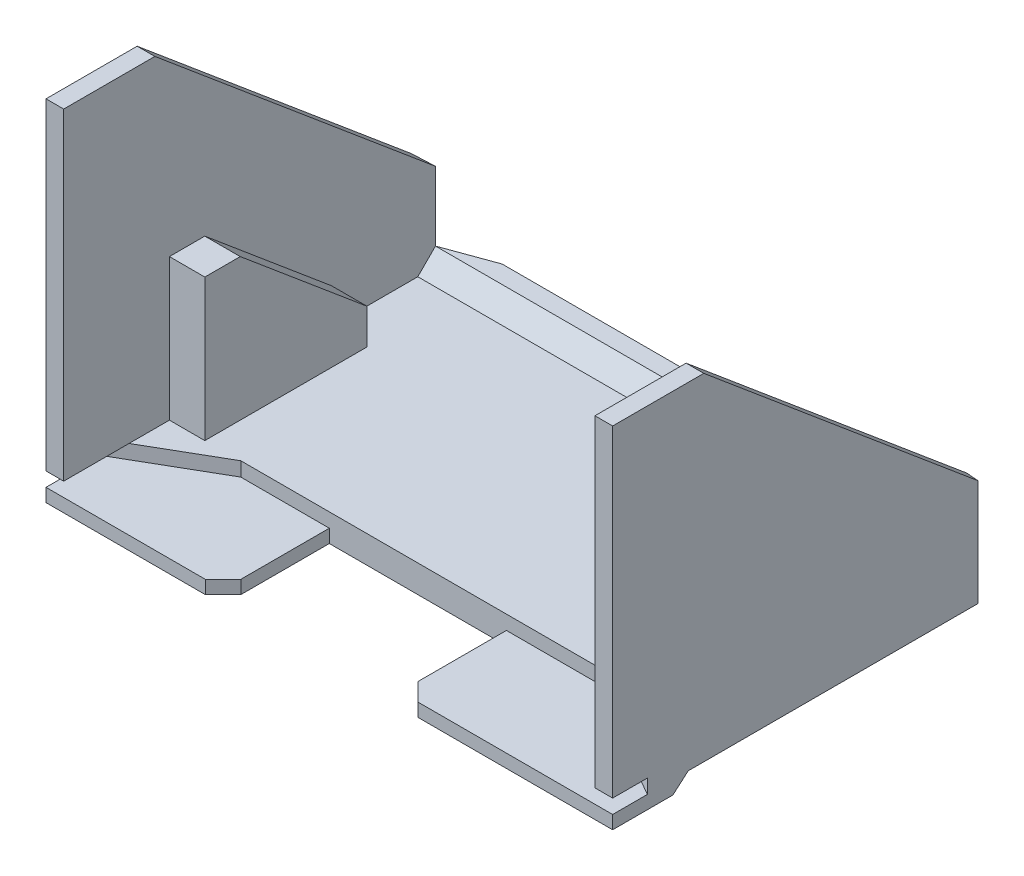
SolidWorks part; units mm, degrees
ref_plane "Front Plane" through (0, 0, 0) normal (0, 0, 1) x (1, 0, 0)
ref_plane "Top Plane" through (0, 0, 0) normal (0, 1, 0) x (1, 0, 0)
ref_plane "Right Plane" through (0, 0, 0) normal (1, 0, 0) x (0, 0, -1)
sketch "Sketch1" plane through (0, 0, 0) normal (1, 0, 0) x (0, 0, -1)
  line L0 (0, 38) -> (0, 0)
  line L1 (0, 0) -> (44, 0)
  line L2 (44, 0) -> (44, 9.7173)
  line L3 (44, 9.7173) -> (10.294, 38)
  line L4 (10.294, 38) -> (0, 38)
  dimension "D1" = 44
  dimension "D2" = 38
  dimension "D3" = 40
  dimension "D4" = 44
extrude "Boss-Extrude1" add sketch "Sketch1" along normal blind 34 and the other way blind 30
sketch "Sketch2" plane through (0, 38, 0) normal (0, 1, 0) x (1, 0, 0)
  line L1 (-30, 44) -> (34, 44) construction
  line L4 (32, 44) -> (-28, 44)
  line L8 (-28, 44) -> (-28, 0)
  line L9 (-30, 0) -> (34, 0) construction
  line L10 (-28, 0) -> (32, 0)
  line L11 (32, 0) -> (32, 44)
  line L12 (-30, 44) -> (-30, 10.294) construction
  line L13 (34, 44) -> (34, 10.294) construction
  dimension "D1" = 2
  dimension "D2" = 2
extrude "Cut-Extrude1" cut sketch "Sketch2" against normal blind 36.4
sketch "Sketch5" plane through (0, 0, 0) normal (0, -1, 0) x (1, 0, 0)
  line L0 (-20, -12) -> (20, -12)
  line L1 (-20, -12) -> (-30, -6.2265)
  line L2 (-30, 0) -> (-30, -44) construction
  line L3 (20, -12) -> (34, -3.9171)
  line L4 (34, 0) -> (34, -44) construction
  line L5 (-30, 0) -> (34, 0) construction
  line L6 (-30, -6.2265) -> (-30, 0)
  line L7 (-30, 0) -> (34, 0)
  line L8 (34, 0) -> (34, -3.9171)
  point P2 (0, -12)
  dimension "D1" = 40
  dimension "D2" = 150
  dimension "D3" = 150
  dimension "D4" = 12
extrude "Cut-Extrude2" cut sketch "Sketch5" against normal up to surface (1.6 mm away) up to face at (2, 1.6, -22)
sketch "Sketch6" plane through (0, 0, 0) normal (0, -1, 0) x (1, 0, 0)
  line L0 (-30, 0) -> (-30, -8.5359)
  line L1 (-30, -6.2265) -> (-30, -44) construction
  line L2 (-30, -8.5359) -> (-20.5359, -14)
  line L3 (-20.5359, -14) -> (20.5359, -14)
  line L4 (20.5359, -14) -> (34, -6.2265)
  line L5 (34, -3.9171) -> (34, -44) construction
  line L6 (34, -6.2265) -> (34, 0)
  line L14 (-28, 0) -> (-30, 0) construction
  line L15 (-30, 0) -> (-30, -6.2265) construction
  line L17 (20, -12) -> (34, -3.9171) construction
  line L18 (-30, -6.2265) -> (-20, -12) construction
  line L19 (-20, -12) -> (20, -12) construction
  line L20 (-30, 0) -> (34, 0)
  dimension "D1" = 2
  dimension "D2" = 2
  dimension "D3" = 2
extrude "Boss-Extrude2" add sketch "Sketch6" along normal blind 1.5
chamfer "Chamfer1" distance 2 angle 45 3 edges at (27.2679, 0, -10.1132) (-25.2679, 0, -11.2679) (0, 0, -14)
sketch "Sketch7" plane through (0, 38, 0) normal (0, 1, 0) x (1, 0, 0)
  line L0 (-30, 41.2638) -> (-22.4825, 44)
  line L1 (-30, 10.8453) -> (-30, 44) construction
  line L2 (-30, 44) -> (34, 44) construction
  line L3 (-30, 41.2638) -> (-30, 44)
  line L4 (26.4825, 44) -> (34, 41.2638)
  line L5 (34, 8.5359) -> (34, 44) construction
  line L6 (34, 41.2638) -> (34, 44)
  line L7 (34, 44) -> (26.4825, 44)
  line L8 (-30, 44) -> (-22.4825, 44)
  dimension "D1" = 8
  dimension "D2" = 160
  dimension "D3" = 160
extrude "Cut-Extrude3" cut sketch "Sketch7" against normal up to surface (38 mm away) up to face at (1.3333, 0, -23.2302)
sketch "Sketch8" plane through (0, 0, 0) normal (0, 1, 0) x (1, 0, 0)
  line L0 (-10, 12) -> (10, 12)
  line L1 (-20, 12) -> (20, 12) construction
  line L2 (10, 12) -> (10, 0)
  line L3 (34, 0) -> (-30, 0) construction
  line L4 (-10, 12) -> (-10, 0)
  line L5 (-10, 0) -> (10, 0)
  dimension "D1" = 20
  dimension "D2" = 10
extrude "Cut-Extrude4" cut sketch "Sketch8" against normal up to surface (1.5 mm away) up to face at (1.3333, -1.5, -7.4862)
sketch "Sketch11" plane through (-28, 0, 0) normal (1, 0, 0) x (0, 0, -1)
  line L0 (15.9371, 17.6) -> (30.2382, 5.6)
  line L1 (30.2382, 5.6) -> (30.2382, 1.6)
  line L2 (30.2382, 1.6) -> (11.9371, 1.6)
  line L3 (11.9371, 1.6) -> (11.9371, 17.6)
  line L4 (11.9371, 17.6) -> (15.9371, 17.6)
  line L5 (41.2638, 12.0133) -> (10.294, 38) construction
  line L6 (8.5359, 0) -> (41.2638, 0) construction
  dimension "D1" = 12
  dimension "D2" = 1.6
  dimension "D3" = 4
  dimension "D4" = 4
  dimension "D5" = 16
extrude "Boss-Extrude3" add sketch "Sketch11" along normal up to surface (60 mm away) up to face at (32, 15.3671, -16.5582)
sketch "Sketch12" plane through (0, 17.6, 0) normal (0, 1, 0) x (1, 0, 0)
  line L0 (-24, 30.2382) -> (-24, 11.9371)
  line L1 (32, 30.2382) -> (-28, 30.2382) construction
  line L2 (32, 11.9371) -> (-28, 11.9371) construction
  line L3 (-24, 11.9371) -> (28, 11.9371)
  line L4 (32, 11.9371) -> (20.1089, 11.9371) construction
  line L5 (28, 11.9371) -> (28, 30.2382)
  line L6 (28, 30.2382) -> (-24, 30.2382)
  line L7 (-28, 41.9918) -> (-28, 10.294) construction
  line L8 (32, 10.294) -> (32, 41.9918) construction
  dimension "D1" = 4
  dimension "D2" = 4
extrude "Cut-Extrude7" cut sketch "Sketch12" against normal up to surface (16 mm away) up to face at (2, 1.6, -38.7433)
chamfer "Chamfer2" distance 2 angle 45 2 edges at (10, -0.75, 0) (-10, -0.75, 0)
sketch "Sketch14" plane through (-28, 0, 0) normal (1, 0, 0) x (0, 0, -1)
  line L6 (41.9918, 3.6) -> (41.9918, 1.6)
  line L7 (41.9918, 11.4024) -> (41.9918, 1.6) construction
  line L8 (41.9918, 1.6) -> (39.9918, 1.6)
  line L9 (39.9918, 1.6) -> (41.9918, 3.6)
  dimension "D1" = 45
  dimension "D2" = 2
extrude "Boss-Extrude4" add sketch "Sketch14" along normal up to surface (60 mm away) up to face at (32, 12.382, -18.1488)
sketch "Sketch15" plane through (0, 1.6, 0) normal (0, 1, 0) x (1, 0, 0)
  line L0 (-28, 41.9918) -> (32, 41.9918)
  line L1 (32, 41.9918) -> (26.4825, 44)
  line L2 (26.4825, 44) -> (-22.4825, 44)
  line L3 (-22.4825, 44) -> (-28, 41.9918)
extrude "Boss-Extrude5" add sketch "Sketch15" along normal up to vertex (2 mm away) up to point (-28, 3.6, -41.9918)
